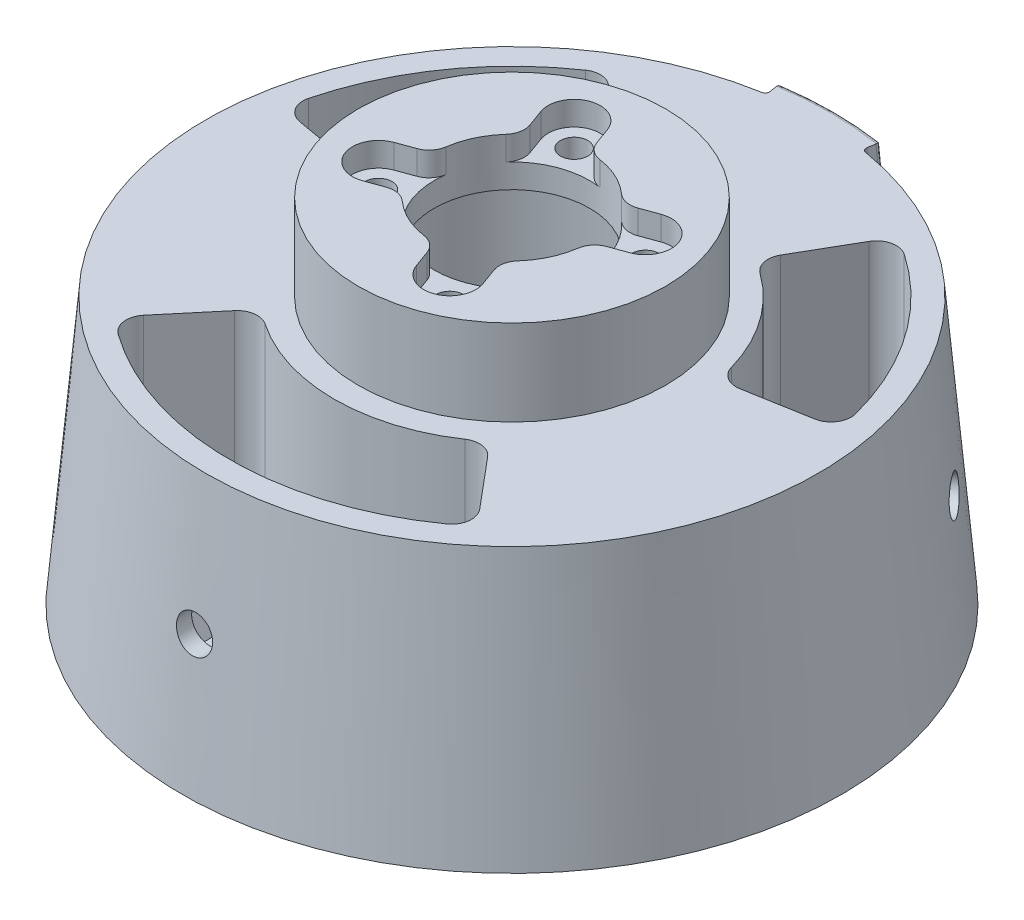
SolidWorks part; units mm, degrees
ref_plane "Front Plane" through (0, 0, 0) normal (0, 0, 1) x (1, 0, 0)
ref_plane "Top Plane" through (0, 0, 0) normal (0, 1, 0) x (1, 0, 0)
ref_plane "Right Plane" through (0, 0, 0) normal (1, 0, 0) x (0, 0, -1)
sketch "Sketch1" plane through (0, 0, 0) normal (0, 1, 0) x (1, 0, 0)
  line L0 (-29.85, 23.9174) -> (-29.85, -23.9174)
  line L1 (29.85, 23.9174) -> (29.85, -23.9174)
  line L2 (-29.85, 0) -> (29.85, 0) construction
  arc A0 (-29.85, -23.9174) -> (29.85, -23.9174) centre (0, 0) ccw
  arc A1 (29.85, 23.9174) -> (-29.85, 23.9174) centre (0, 0) ccw
  point P9 (0, 0)
  dimension "D1" = 59.7
  dimension "D2" = 76.5
extrude "Boss-Extrude1" add sketch "Sketch1" along normal blind 44
sketch "Sketch2" plane through (0, 44, 0) normal (0, 1, 0) x (1, 0, 0)
  line L0 (-4.4463, 12.216) -> (0, 0) construction
  line L1 (0, 13) -> (0, 0) construction
  circle A0 centre (0, 0) radius 13
  point P3 (-4.4463, 12.216)
  dimension "D1" = 26
  dimension "D2" = 20
hole_wizard "CBORE for M3 SHCS1" positions "Sketch2" profile "Sketch3" counterbore size "M3" standard "ANSI Metric" end condition through all
sketch "Sketch3" plane through (-4.4463, 44, -12.216) normal (1, 0, 0) x (0, 0, 1)
  line L0 (0, 0) -> (0, 44)
  line L1 (0, 44) -> (1.7, 44)
  line L3 (1.7, 44) -> (1.7, 3)
  line L4 (1.7, 3) -> (3.25, 3)
  line L5 (3.25, 3) -> (3.25, 0)
  line L7 (3.25, 0) -> (0, 0)
  line L11 (0, -6.35) -> (0, 107.95) construction
  dimension "Thru Hole Dia." = 3.4
  dimension "Thru Hole Depth" = 44
  dimension "C'Bore Dia." = 6.5
  dimension "C'Bore Depth" = 3
ref_axis "Axis1" through (0, 44, 0) along (0, -1, 0)
pattern_circular "CirPattern1" count 4 over 360 about axis through (0, 44, 0) along (0, -1, 0) of "CBORE for M3 SHCS1"
sketch "Sketch4" plane through (0, 0, 0) normal (0, -1, 0) x (1, 0, 0)
  circle A0 centre (0, 0) radius 16.2
  dimension "D1" = 32.4
extrude "Cut-Extrude1" cut sketch "Sketch4" against normal blind 38
sketch "Sketch5" plane through (0, 44, 0) normal (0, 1, 0) x (1, 0, 0)
  circle A0 centre (0, 0) radius 9.7
extrude "Cut-Extrude2" cut sketch "Sketch5" against normal through all
ref_plane "Plane1" through (0, 0, -38.25) normal (0, 0, -1) x (-1, 0, 0)
sketch "Sketch7" plane through (0, 0, 0) normal (0, -1, 0) x (1, 0, 0)
  line L5 (29.85, 23.9174) -> (29.85, -23.9174)
  line L6 (-29.85, 23.9174) -> (-29.85, -23.9174)
  arc A0 (-29.85, -23.9174) -> (29.85, -23.9174) centre (0, 0) ccw construction
  arc A1 (29.85, 23.9174) -> (-29.85, 23.9174) centre (0, 0) ccw construction
  arc A2 (-29.85, -23.9174) -> (29.85, -23.9174) centre (0, 0) ccw
  arc A3 (29.85, 23.9174) -> (-29.85, 23.9174) centre (0, 0) ccw
  circle A4 centre (0, 0) radius 41.1622
  dimension "D1" = 82.3245
extrude "Boss-Extrude2" add sketch "Sketch7" against normal up to surface (44 mm away) up to face at (0, 44, 9.7)
sketch "Sketch9" plane through (0, 0, 0) normal (1, 0, 0) x (0, 0, -1)
  line L0 (-41.1622, 0) -> (-37.3127, 44)
  line L1 (-37.3127, 44) -> (-41.1622, 44)
  line L2 (-41.1622, 44) -> (-41.1622, 0) construction
  line L3 (-41.1622, 44) -> (-41.1622, 0)
  line L4 (0, 0) -> (0, 44) construction
  line L5 (41.1622, 44) -> (-41.1622, 44) construction
  point P14 (-38.0619, 35.4368)
  dimension "D1" = 5
revolve "Cut-Revolve2" cut sketch "Sketch9" angle 360 about L4
sketch "Sketch10" plane through (0, 0, 0) normal (1, 0, 0) x (0, 0, -1)
  line L0 (-19.2, 44) -> (-19.2, 33.2871)
  line L1 (37.3127, 44) -> (-37.3127, 44) construction
  line L2 (-19.2, 33.2871) -> (-38.25, 33.2871)
  line L3 (-37.3127, 44) -> (-41.1622, 0) construction
  line L4 (-38.25, 33.2871) -> (-37.3127, 44)
  line L5 (-37.3127, 44) -> (-19.2, 44)
  line L6 (0, 0) -> (0, 44) construction
  line L10 (-41.1622, 0) -> (41.1622, 0) construction
  line L11 (-16.2, 0) -> (16.2, 0) construction
  line L12 (-16.2, 0) -> (16.2, 0) construction
  line L13 (37.3127, 44) -> (-37.3127, 44) construction
  dimension "D1" = 10.7129
  dimension "D2" = 33.2871
  dimension "D3" = 3
revolve "Cut-Revolve3" cut sketch "Sketch10" angle 360 about L6
sketch "Sketch13" plane through (0, 33.2871, 0) normal (0, 1, 0) x (1, 0, 0)
  line L0 (0, -35.25) -> (0, -38.25) construction
  circle A0 centre (0, 0) radius 35.25
  circle A1 centre (0, 0) radius 19.2 construction
  circle A2 centre (0, 0) radius 19.2
  circle A3 centre (0, 0) radius 38.25 construction
  dimension "D1" = 3
extrude "Cut-Extrude3" cut sketch "Sketch13" against normal through all both and the other way through all
sketch "Sketch16" plane through (0, 0, 0) normal (0, -1, 0) x (1, 0, 0)
  line L0 (0, -35.25) -> (0, -19.2) construction
  line L1 (-17.625, -30.5274) -> (-9.6, -16.6277)
  line L2 (17.625, -30.5274) -> (9.6, -16.6277)
  line L3 (-34.7145, -6.1211) -> (-18.9083, -3.334)
  line L4 (-22.6583, 27.0031) -> (-12.3415, 14.7081)
  line L5 (22.6583, 27.0031) -> (12.3415, 14.7081)
  line L6 (34.7145, -6.1211) -> (18.9083, -3.334)
  line L7 (0, 0) -> (-33.1242, 12.0562) construction
  circle A1 centre (0, 0) radius 35.25 construction
  circle A2 centre (0, 0) radius 19.2 construction
  arc A3 (-9.6, -16.6277) -> (9.6, -16.6277) centre (0, 0) ccw
  arc A4 (-17.625, -30.5274) -> (17.625, -30.5274) centre (0, 0) ccw
  arc A5 (-22.6583, 27.0031) -> (-34.7145, -6.1211) centre (0, 0) ccw
  arc A6 (-12.3415, 14.7081) -> (-18.9083, -3.334) centre (0, 0) ccw
  arc A7 (22.6583, 27.0031) -> (34.7145, -6.1211) centre (0, 0) cw
  arc A8 (12.3415, 14.7081) -> (18.9083, -3.334) centre (0, 0) cw
  point P19 (0, 0)
  dimension "D1" = 16.05
  dimension "D3" = 60
  dimension "D4" = 110
  dimension "D2" = 2
extrude "Boss-Extrude4" add sketch "Sketch16" against normal up to surface (33.2871 mm away) up to face at (0, 33.2871, 35.25)
sketch "Sketch17" plane through (0, 33.2871, 0) normal (0, 1, 0) x (1, 0, 0)
  line L0 (0, -19.2) -> (0, -22.2) construction
  circle A0 centre (0, 0) radius 22.2
  circle A1 centre (0, 0) radius 19.2 construction
  circle A2 centre (0, 0) radius 19.2
  dimension "D1" = 3
extrude "Boss-Extrude5" add sketch "Sketch17" against normal up to surface (33.2871 mm away) up to face at (-21.2567, 0, -14.8841)
fillet "Fillet2" radius 2.5 12 edges at (-14.2699, 16.6435, 17.0062) (-22.6583, 16.6435, 27.0031) (22.6583, 16.6435, 27.0031) (14.2699, 16.6435, 17.0062) (-17.625, 16.6435, -30.5274) (-34.7145, 16.6435, -6.1211) (-21.8627, 16.6435, -3.855) (-11.1, 16.6435, -19.2258) (34.7145, 16.6435, -6.1211) (17.625, 16.6435, -30.5274) (11.1, 16.6435, -19.2258) (21.8627, 16.6435, -3.855)
ref_plane "Plane2" through (0, 16.6435, 0) normal (0, -1, 0) x (-1, 0, 0)
sketch "Sketch18" plane through (0, 16.6435, 0) normal (0, -1, 0) x (-1, 0, 0)
  line L0 (0, 0) -> (28.8751, 20.2186) construction
  line L1 (0, 0) -> (-28.8751, 20.2186) construction
  line L2 (0, 0) -> (0, -35.25) construction
  line L3 (0, 0) -> (-10.7822, -33.5605) construction
  line L4 (0, 0) -> (10.7822, -33.5605) construction
  arc A0 (34.1459, 8.7532) -> (19.9039, 29.0929) centre (0, 0) ccw construction
  arc A1 (-19.9039, 29.0929) -> (-34.1459, 8.7532) centre (0, 0) ccw construction
  arc A2 (-20.5308, -28.6539) -> (20.5308, -28.6539) centre (0, 0) ccw construction
  arc A3 (-20.5308, -28.6539) -> (0, -35.25) centre (0, 0) ccw construction
  arc A4 (0, -35.25) -> (20.5308, -28.6539) centre (0, 0) ccw construction
  point P18 (0, 0)
ref_plane "Plane4" through (-28.8751, 16.6435, -20.2186) normal (-0.8192, 0, -0.5736) x (-0.5736, 0, 0.8192)
sketch "Sketch20" plane through (-28.8751, 16.6435, -20.2186) normal (-0.8192, 0, -0.5736) x (-0.5736, 0, 0.8192)
  circle A0 centre (0, 0) radius 2.25
  dimension "D1" = 4.5
extrude "Cut-Extrude5" cut sketch "Sketch20" against normal blind 10 and the other way through all
sketch "Sketch21" plane through (-28.8751, 16.6435, -20.2186) normal (-0.8192, 0, -0.5736) x (-0.5736, 0, 0.8192)
  line L1 (4.0415, 0) -> (2.0207, 3.5)
  line L2 (2.0207, 3.5) -> (-2.0207, 3.5)
  line L3 (-2.0207, 3.5) -> (-4.0415, 0)
  line L4 (-4.0415, 0) -> (-2.0207, -3.5)
  line L5 (-2.0207, -3.5) -> (2.0207, -3.5)
  line L6 (2.0207, -3.5) -> (4.0415, 0)
  circle A0 centre (0, 0) radius 3.5 construction
  dimension "D1" = 4.0415
  dimension "D2" = 7
extrude "Cut-Extrude6" cut sketch "Sketch21" against normal blind 10 and the other way blind 2.5
pattern_circular "CirPattern2" count 3 over 250 about axis through (0, 0, 0) along (0, 1, 0) of "Cut-Extrude5", "Cut-Extrude6"
sketch "Sketch22" plane through (0, 44, 0) normal (0, 1, 0) x (1, 0, 0)
  line L2 (-12.216, -4.4463) -> (12.216, 4.4463) construction
  line L3 (-13.3276, -1.3923) -> (11.1044, 7.5003) construction
  line L4 (-11.1044, -7.5003) -> (13.3276, 1.3923) construction
  line L5 (-4.4463, 12.216) -> (4.4463, -12.216) construction
  line L6 (-1.3923, 13.3276) -> (7.5003, -11.1044) construction
  line L7 (-7.5003, 11.1044) -> (1.3923, -13.3276) construction
  line L8 (-11.1044, -7.5003) -> (-1.9424, -4.1656)
  line L9 (-1.9424, -4.1656) -> (1.3923, -13.3276)
  line L10 (7.5003, -11.1044) -> (4.1656, -1.9424)
  line L11 (4.1656, -1.9424) -> (13.3276, 1.3923)
  line L12 (11.1044, 7.5003) -> (1.9424, 4.1656)
  line L13 (1.9424, 4.1656) -> (-1.3923, 13.3276)
  line L14 (-7.5003, 11.1044) -> (-4.1656, 1.9424)
  line L15 (-4.1656, 1.9424) -> (-13.3276, -1.3923)
  arc A0 (-13.3276, -1.3923) -> (-11.1044, -7.5003) centre (-12.216, -4.4463) ccw
  arc A1 (1.3923, -13.3276) -> (7.5003, -11.1044) centre (4.4463, -12.216) ccw
  arc A2 (13.3276, 1.3923) -> (11.1044, 7.5003) centre (12.216, 4.4463) ccw
  arc A3 (-1.3923, 13.3276) -> (-7.5003, 11.1044) centre (-4.4463, 12.216) ccw
  arc A10 (-13.3276, -1.3923) -> (-11.1044, -7.5003) centre (-12.216, -4.4463) ccw construction
  arc A11 (13.3276, 1.3923) -> (11.1044, 7.5003) centre (12.216, 4.4463) ccw construction
  circle A12 centre (12.216, 4.4463) radius 3.25 construction
  arc A13 (-1.3923, 13.3276) -> (-7.5003, 11.1044) centre (-4.4463, 12.216) ccw construction
  arc A14 (1.3923, -13.3276) -> (7.5003, -11.1044) centre (4.4463, -12.216) ccw construction
  circle A15 centre (4.4463, -12.216) radius 3.25 construction
  point P2 (0, 0)
  point P11 (0, 0)
extrude "temporary_probnably" cut sketch "Sketch22" against normal up to surface (3 mm away) up to face at (-4.4463, 41, -10.516)
fillet "also_probably_temporary" radius 2.5 8 edges at (-9.6997, 42.5, 0.0718) (-7.4766, 42.5, 6.1798) (0.0718, 42.5, 9.6997) (6.1798, 42.5, 7.4766) (9.6997, 42.5, -0.0718) (7.4766, 42.5, -6.1798) (-0.0718, 42.5, -9.6997) (-6.1798, 42.5, -7.4766)
sketch "Sketch24" plane through (0, 0, 0) normal (1, 0, 0) x (0, 0, -1)
  line L0 (38.25, 33.2871) -> (-38.25, 33.2871) construction
  line L1 (-41.1622, 0) -> (41.1622, 0) construction
  line L2 (38.25, 33.2871) -> (-38.25, 33.2871) construction
  line L3 (-41.1622, 0) -> (41.1622, 0) construction
  line L4 (41.1622, 0) -> (43.1622, 0)
  line L5 (38.25, 33.2871) -> (40.25, 33.2871)
  line L6 (38.25, 33.2871) -> (41.1622, 0)
  line L7 (40.25, 33.2871) -> (43.1622, 0)
  line L8 (0, 33.2871) -> (0, 0) construction
  dimension "D1" = 2
revolve "key_1" add sketch "Sketch24" angle 9 about L8 other way angle 9
fillet "key_2" radius 0.5 6 edges at (0, 0, -43.1622) (0, 33.2871, -40.25) (-6.5243, 16.6435, -41.1926) (6.5243, 16.6435, -41.1926) (-6.2114, 16.6435, -39.2173) (6.2114, 16.6435, -39.2173)
